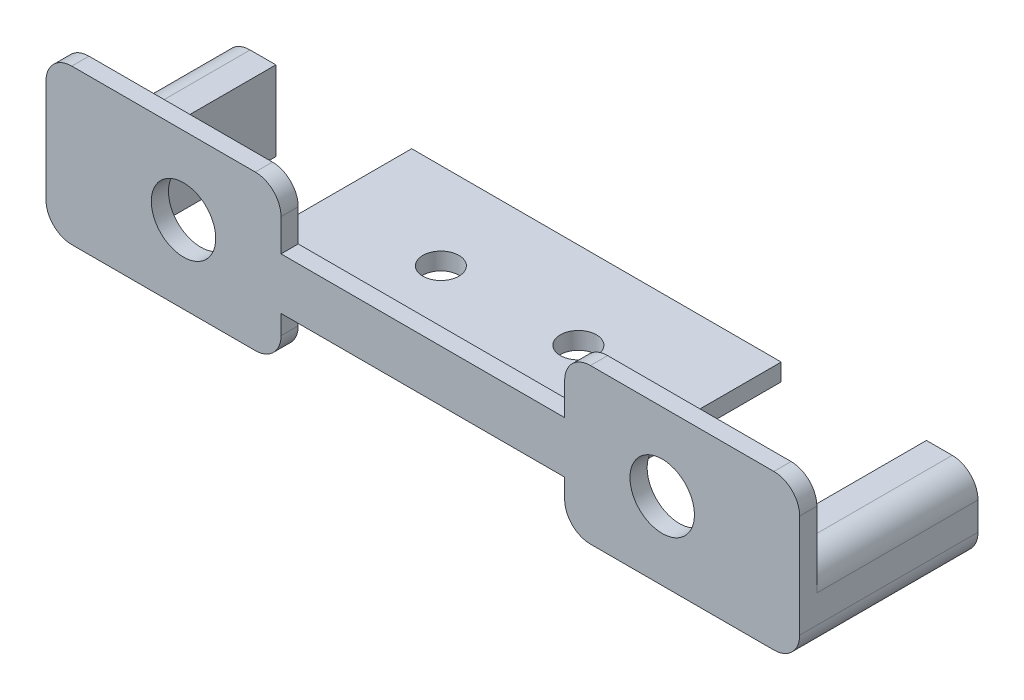
SolidWorks part; units mm, degrees
ref_plane "Front Plane" through (0, 0, 0) normal (0, 0, 1) x (1, 0, 0)
ref_plane "Top Plane" through (0, 0, 0) normal (0, 1, 0) x (1, 0, 0)
ref_plane "Right Plane" through (0, 0, 0) normal (1, 0, 0) x (0, 0, -1)
sketch "Sketch3" plane through (0, 0, 0) normal (0, 1, 0) x (1, 0, 0)
  line L1 (-21.5, 0) -> (21.5, 0)
  line L2 (-21.5, 0) -> (-21.5, 18.2)
  line L3 (-21.5, 18.2) -> (21.5, 18.2)
  line L4 (21.5, 0) -> (21.5, 18.2)
  line L5 (-8, 8.1) -> (8, 8.1) construction
  circle A0 centre (-8, 8.1) radius 2.1
  circle A1 centre (8, 8.1) radius 2.1
  point P6 (0, 0)
  point P12 (0, 8.1)
  dimension "D2" = 4.2
  dimension "D1" = 16
  dimension "D3" = 8
  dimension "D4" = 6
  dimension "D5" = 43
extrude "Boss-Extrude5" add sketch "Sketch3" against normal blind 2 separate body
sketch "Sketch1" plane through (0, 0, 0) normal (0, 0, 1) x (1, 0, 0)
  line L0 (0, -1000) -> (0, 49000) construction
  line L1 (-43.85, -9.25) -> (-16.5, -9.25)
  line L2 (-43.85, -9.25) -> (-43.85, 8.75)
  line L4 (43.85, -9.25) -> (43.85, 8.75)
  line L5 (-43.85, -0.25) -> (43.85, -0.25) construction
  line L6 (-43.85, 8.75) -> (-16.5, 8.75)
  line L15 (-37.85, -24) -> (-37.85, 0) construction
  line L16 (-16.5, 8.75) -> (-16.5, 2)
  line L17 (-16.5, -9.25) -> (-16.5, -4)
  line L18 (-16.5, -4) -> (16.5, -4)
  line L19 (16.5, -4) -> (16.5, -9.25)
  line L20 (16.5, -9.25) -> (43.85, -9.25)
  line L21 (-16.5, 2) -> (16.5, 2)
  line L22 (-21.5, -2) -> (21.5, -2) construction
  line L23 (-21.5, 0) -> (21.5, 0) construction
  line L24 (-21.5, -2) -> (-21.5, 0) construction
  line L25 (16.5, 2) -> (16.5, 8.75)
  line L26 (16.5, 8.75) -> (43.85, 8.75)
  circle A0 centre (-27.85, -0.25) radius 3.75
  circle A2 centre (27.85, -0.25) radius 3.75
  point P14 (0, -4)
  point P32 (0, 2)
  dimension "D3" = 7.5
  dimension "D4" = 10
  dimension "D1" = 18
  dimension "D2" = 6
  dimension "D5" = 5
  dimension "D6" = 2
  dimension "D7" = 4
  dimension "D8" = 5
  dimension "D9" = 2
extrude "Boss-Extrude1" add sketch "Sketch1" along normal blind 2
chamfer "Chamfer1" distance 1.5 angle 45 1 edges at (0, -2, 0)
sketch "Sketch5" plane through (0, 0, 0) normal (0, 0, -1) x (-1, 0, 0)
  line L0 (43.85, -9.25) -> (16.5, -9.25) construction
  line L1 (43.85, 0) -> (37.85, 0)
  line L2 (43.85, 0) -> (43.85, -9.25)
  line L3 (43.85, -9.25) -> (37.85, -9.25)
  line L4 (37.85, 0) -> (37.85, -9.25)
  line L5 (37.85, -24) -> (37.85, 0) construction
  line L6 (37.85, 0) -> (60.85, 0) construction
extrude "Boss-Extrude4" add sketch "Sketch5" along normal up to surface (18.75 mm away)
mirror "Mirror2" about plane through (0, 0, 0) normal (1, 0, 0) of "Boss-Extrude4"
fillet "Fillet1" radius 3 10 edges at (-43.85, -9.25, -8.375) (-43.85, 8.75, 1) (-43.85, 0, -9.375) (43.85, 0, -9.375) (43.85, -9.25, -8.375) (43.85, 8.75, 1) (16.5, -9.25, 1) (16.5, 8.75, 1) (-16.5, 8.75, 1) (-16.5, -9.25, 1)
equation "\"width\"= 24"
equation "\"thk\"= 3"
equation "\"holesize\"= 4.2"
equation "\"holedistance\"= ( 20 + 12 ) / 2"
equation "\"threaded_hole\"= 3.9"
equation "\"fillet_radius\"= 2"
equation "\"ground_clearance\"= 25"
equation "\"tire_thk\"= 3"
equation "\"innerwheel_diam\" = \"wheel_diam\"-2*\"tire_thk\""
equation "\"innerwheel_thk\"= 8"
equation "\"wheel_diam\"= 2*(\"width\"/2+\"ground_clearance\")"
equation "\"coloursensor_holesize\"= 2.65"
equation "\"hole_to_edge\" = 4"
equation "\"D1@Sketch3\"=\"holedistance\""
equation "\"D2@Sketch3\"=\"holesize\""
